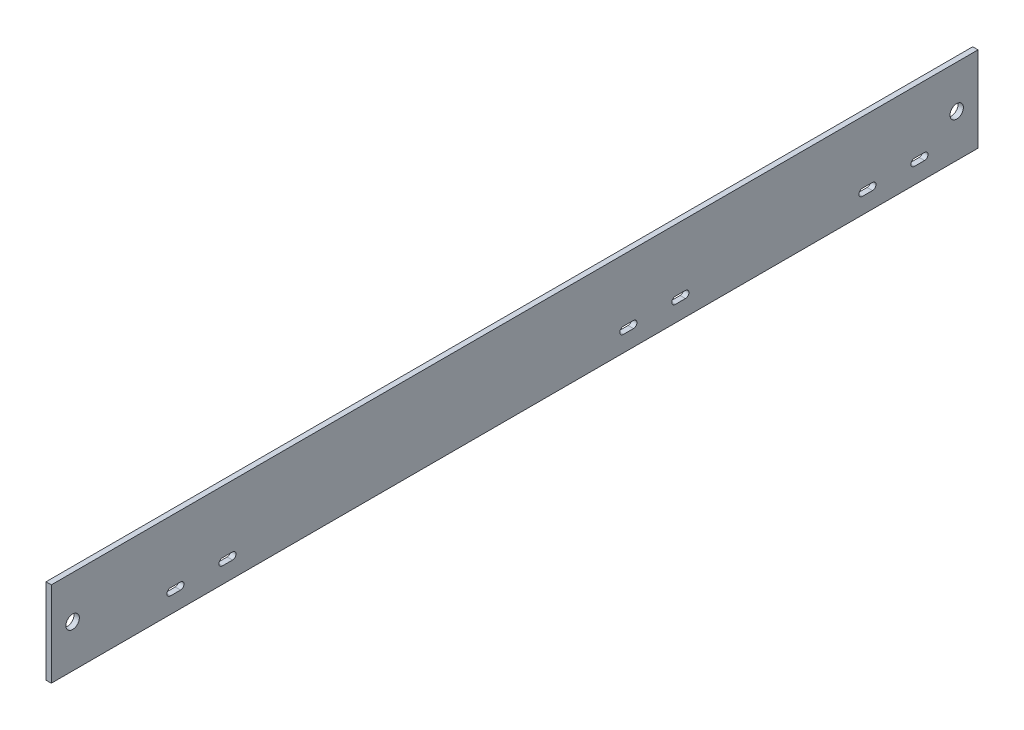
SolidWorks part; units mm, degrees
ref_plane "Front Plane" through (0, 0, 0) normal (0, 0, 1) x (1, 0, 0)
ref_plane "Top Plane" through (0, 0, 0) normal (0, 1, 0) x (1, 0, 0)
ref_plane "Right Plane" through (0, 0, 0) normal (1, 0, 0) x (0, 0, -1)
sketch "Sketch1" plane through (0, 0, 0) normal (1, 0, 0) x (0, 0, -1)
  line L0 (71.025, 11.7) -> (77.025, 11.7) construction
  line L1 (0, 0) -> (552.45, 0)
  line L2 (0, 0) -> (0, 50.8)
  line L3 (0, 50.8) -> (552.45, 50.8)
  line L4 (552.45, 0) -> (552.45, 50.8)
  line L5 (71.025, 13.8) -> (77.025, 13.8)
  line L6 (71.025, 9.6) -> (77.025, 9.6)
  line L7 (102.025, 11.7) -> (108.025, 11.7) construction
  line L8 (102.025, 13.8) -> (108.025, 13.8)
  line L9 (102.025, 9.6) -> (108.025, 9.6)
  line L10 (341.025, 11.7) -> (347.025, 11.7) construction
  line L11 (341.025, 13.8) -> (347.025, 13.8)
  line L12 (341.025, 9.6) -> (347.025, 9.6)
  line L13 (372.025, 11.7) -> (378.025, 11.7) construction
  line L14 (372.025, 13.8) -> (378.025, 13.8)
  line L15 (372.025, 9.6) -> (378.025, 9.6)
  line L16 (483.55, 11.7) -> (489.55, 11.7) construction
  line L17 (483.55, 13.8) -> (489.55, 13.8)
  line L18 (483.55, 9.6) -> (489.55, 9.6)
  line L19 (514.55, 11.7) -> (520.55, 11.7) construction
  line L20 (514.55, 13.8) -> (520.55, 13.8)
  line L21 (514.55, 9.6) -> (520.55, 9.6)
  circle A0 centre (12.7, 25.4) radius 4
  circle A1 centre (539.75, 25.4) radius 4
  arc A2 (71.025, 13.8) -> (71.025, 9.6) centre (71.025, 11.7) ccw
  arc A3 (77.025, 9.6) -> (77.025, 13.8) centre (77.025, 11.7) ccw
  arc A4 (102.025, 13.8) -> (102.025, 9.6) centre (102.025, 11.7) ccw
  arc A5 (108.025, 9.6) -> (108.025, 13.8) centre (108.025, 11.7) ccw
  arc A6 (341.025, 13.8) -> (341.025, 9.6) centre (341.025, 11.7) ccw
  arc A7 (347.025, 9.6) -> (347.025, 13.8) centre (347.025, 11.7) ccw
  arc A8 (372.025, 13.8) -> (372.025, 9.6) centre (372.025, 11.7) ccw
  arc A9 (378.025, 9.6) -> (378.025, 13.8) centre (378.025, 11.7) ccw
  arc A12 (483.55, 13.8) -> (483.55, 9.6) centre (483.55, 11.7) ccw
  arc A13 (489.55, 9.6) -> (489.55, 13.8) centre (489.55, 11.7) ccw
  arc A14 (514.55, 13.8) -> (514.55, 9.6) centre (514.55, 11.7) ccw
  arc A15 (520.55, 9.6) -> (520.55, 13.8) centre (520.55, 11.7) ccw
  point P11 (74.025, 11.7)
  point P16 (105.025, 11.7)
  point P23 (344.025, 11.7)
  point P30 (375.025, 11.7)
  point P43 (486.55, 11.7)
  point P48 (517.55, 11.7)
  dimension "D3" = 8
  dimension "D8" = 4.2
  dimension "D1" = 50.8
  dimension "D2" = 552.45
  dimension "D4" = 25.4
  dimension "D5" = 12.7
  dimension "D6" = 12.7
  dimension "D7" = 6
  dimension "D9" = 31
  dimension "D10" = 31
  dimension "D11" = 270
  dimension "D13" = 39.1
  dimension "D12" = 74.025
  dimension "D14" = 539.75
  dimension "D15" = 344.025
  dimension "D16" = 105.025
  dimension "D17" = 375.025
  dimension "D23" = 31
  dimension "D24" = 34.9
  dimension "D25" = 486.55
  dimension "D26" = 517.55
extrude "Boss-Extrude2" add sketch "Sketch1" along normal blind 3.175
equation "\"RailThickness\"= .125in'Spec"
equation "\"VSWidth\"= 1.25in'Spec"
equation "\"SideRailLength\"= 21.75in"
equation "\"LowerRailHeight\"= 2.0in"
equation "\"StepperHolePadSize\"= \"StepperHoleDiameter\""
equation "\"DistanceFromFrontSideToFirstLeftStepperHoleMountYSValue\"= 74.025mm"
equation "\"DistanceBetweenFrontToBackStepperHoles\"= \"BedLength\" - \"BuildPlateStandoffHolesDistanceFromFrontOrBackSide\" * 2'Equals 270"
equation "\"BedLength\"= \"BuildPlateLength\""
equation "\"D1@Sketch1\"=\"LowerRailHeight\""
equation "\"D2@Sketch1\"=\"SideRailLength\""
equation "\"FrameFastenerHoleDiameter\"= 8mm"
equation "\"D3@Sketch1\"=\"FrameFastenerHoleDiameter\""
equation "\"D4@Sketch1\"=\"LowerRailHeight\"/2"
equation "\"D5@Sketch1\"=\"FrameFastenerHoleOffsetFromEdge\""
equation "\"D6@Sketch1\"=\"FrameFastenerHoleOffsetFromEdge\""
equation "\"D8@Sketch1\"=\"StepperMountSlotDiameterOnRails\""
equation "\"D11@Sketch1\"=\"DistanceBetweenFrontToBackStepperHoles\""
equation "\"D1@Boss-Extrude2\"=\"RailThickness\""
equation "\"FrameFastenerHoleOffsetFromEdge\"= \"VSWidth\" / 2 - \"GapBetweenVerticalSupportsAndRails\" / 2"
equation "\"StepperMountSlotDiameterOnRails\"= 4.2mm"
equation "\"StepperMountSlotWidth\"= 6mm"
equation "\"D7@Sketch1\"=\"StepperMountSlotWidth\""
equation "\"Nema17StepperMountSlotDistance\"= 31mm'Spec"
equation "\"D9@Sketch1\"=\"Nema17StepperMountSlotDistance\""
equation "\"D10@Sketch1\"=\"Nema17StepperMountSlotDistance\""
equation "\"BuildPlateLength\"= 352mm'Spec"
equation "\"BuildPlateStandoffHolesDistanceFromFrontOrBackSide\"= 41mm"
equation "\"D13@Sketch1\"=\"OffsetToGive10mmZAxisMovement\""
equation "\"D12@Sketch1\"=\"DistanceFromFrontSideToFirstLeftStepperHoleMountYSValue\""
equation "\"OffsetToGive10mmZAxisMovement\"= \"LowerRailHeight\" / 2 + 13.7mm'Allow Stepper 10mm Vertical movement"
equation "\"GapBetweenVerticalSupportsAndRails\"= \"RailThickness\" * 2"
equation "\"AngleBracketSmallHoleDiameter\"= 4mm"
equation "\"AngleBracketSlotDistanceBetweenHoles\"= 30mm"
equation "\"AngleBracketSlotDistanceFromTop\"= 13mm"
equation "\"AngleBracketSlotDistanceFromCorner\"= \"AngleBracketSlotDistanceFromBack\" - \"GapBetweenVerticalSupportsAndRails\" / 2'Equals 61.825"
equation "\"AngleBracketSlotDistanceFromBack\"= 65mm"
equation "\"D23@Sketch1\"=\"Nema17StepperMountSlotDistance\""
equation "\"DistanceFromBackToFirstGantryStepperHole\"= \"VSWidth\" - \"RailThickness\" + ( \"Nema17MountWidth\" - \"Nema17StepperMountSlotDistance\" ) / 2 - \"GapBetweenVerticalSupportsAndRails\" / 2'Equals 34.9. Push Gantry stepper as far back as possible"
equation "\"Nema17MountWidth\"= 50mm"
equation "\"D24@Sketch1\"=\"DistanceFromBackToFirstGantryStepperHole\""
